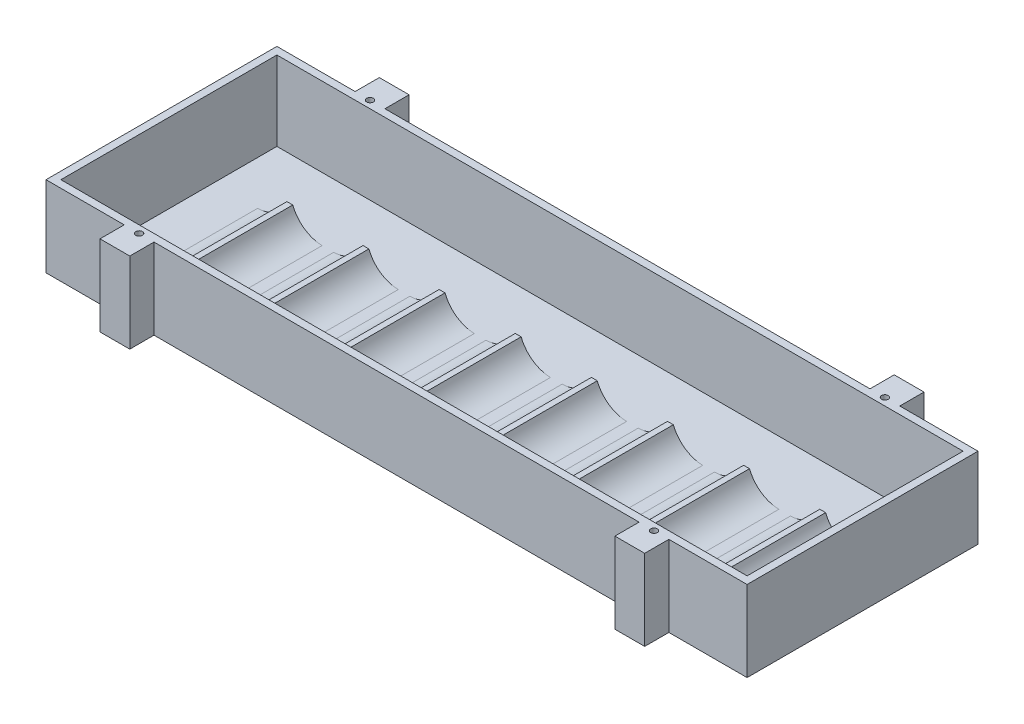
SolidWorks part; units mm, degrees
material "ABS"
ref_plane "Front Plane" through (0, 0, 0) normal (0, 0, 1) x (1, 0, 0)
ref_plane "Top Plane" through (0, 0, 0) normal (0, 1, 0) x (1, 0, 0)
ref_plane "Right Plane" through (0, 0, 0) normal (1, 0, 0) x (0, 0, -1)
sketch "Sketch1" plane through (0, 0, 0) normal (0, 1, 0) x (1, 0, 0)
  line L0 (2.54, -2.54) -> (2.54, -76.2)
  line L1 (0, 0) -> (239.08, 0)
  line L2 (0, 0) -> (0, -78.74)
  line L3 (0, -78.74) -> (239.08, -78.74)
  line L4 (239.08, 0) -> (239.08, -78.74)
  line L5 (2.54, -76.2) -> (236.54, -76.2)
  line L6 (236.54, -2.54) -> (236.54, -76.2)
  line L7 (2.54, -2.54) -> (236.54, -2.54)
  line L8 (0, 0) -> (0, 8.255)
  line L9 (0, 8.255) -> (239.08, 8.255)
  line L10 (239.08, 8.255) -> (239.08, 0)
  line L11 (0, -78.74) -> (0, -86.995)
  line L12 (0, -86.995) -> (239.08, -86.995)
  line L13 (239.08, -86.995) -> (239.08, -78.74)
  dimension "D1" = 73.66
  dimension "D2" = 234
  dimension "D4" = 10.795
  dimension "D5" = 95.25
  dimension "D3" = 2.54
extrude "Boss-Extrude1" add sketch "Sketch1" against normal blind 0.508 contours L2 L3 L4 L1
extrude "Boss-Extrude2" add sketch "Sketch1<3>" along normal blind 27 contours L10 L9 L8 L1 | L12 L13 L3 L11 | L4 L1 L2 L3 L0 L7 L6 L5 region at (119.54, 0, -4.1275) region at (119.54, 0, 2.5171) region at (119.54, 0, 82.8675)
sketch "Sketch1<3>" plane through (0, 0, 0) normal (0, 1, 0) x (1, 0, 0) same geometry as "Sketch1"
sketch "Sketch2" plane through (0, 0, 0) normal (0, 1, 0) x (-1, 0, 0)
  line L0 (-28.54, 0) -> (-28.54, 78.74) construction
  line L1 (-2.54, 2.54) -> (-2.54, 76.2) construction
  line L2 (-17.54, 0) -> (-17.54, 78.74) construction
  line L9 (0, 0) -> (-239.08, 0) construction
  line L10 (0, 78.74) -> (-239.08, 78.74) construction
  dimension "D1" = 26
  dimension "D2" = 15
sketch "Sketch5" plane through (0, 0, 2.54) normal (0, 0, 1) x (1, 0, 0)
  line L0 (28.54, 0) -> (28.54, 7) construction
  line L1 (29.54, 7) -> (27.54, 7)
  line L2 (0, 0) -> (239.08, 0) construction
  line L3 (17.54, 0) -> (39.54, 0)
  line L16 (55.4988, 7) -> (53.4988, 7)
  line L17 (43.4988, 0) -> (65.4988, 0)
  line L18 (54.4988, 0) -> (54.4988, 7) construction
  line L19 (81.4576, 7) -> (79.4576, 7)
  line L20 (69.4576, 0) -> (91.4576, 0)
  line L21 (80.4576, 0) -> (80.4576, 7) construction
  line L22 (107.4164, 7) -> (105.4164, 7)
  line L23 (95.4164, 0) -> (117.4164, 0)
  line L24 (106.4164, 0) -> (106.4164, 7) construction
  line L25 (133.3752, 7) -> (131.3752, 7)
  line L26 (121.3752, 0) -> (143.3752, 0)
  line L27 (132.3752, 0) -> (132.3752, 7) construction
  line L28 (159.334, 7) -> (157.334, 7)
  line L29 (147.334, 0) -> (169.334, 0)
  line L30 (158.334, 0) -> (158.334, 7) construction
  line L37 (170.06, 7) -> (168.06, 7) [skipped]
  line L38 (158.06, 0) -> (180.06, 0) [skipped]
  line L39 (169.06, 0) -> (169.06, 7) construction
  line L40 (145.64, 0) -> (145.64, 7) construction
  line L41 (134.64, 0) -> (156.64, 0) [skipped]
  line L42 (146.64, 7) -> (144.64, 7) [skipped]
  line L43 (122.22, 0) -> (122.22, 7) construction
  line L44 (111.22, 0) -> (133.22, 0) [skipped]
  line L45 (123.22, 7) -> (121.22, 7) [skipped]
  line L46 (98.8, 0) -> (98.8, 7) construction
  line L47 (87.8, 0) -> (109.8, 0) [skipped]
  line L48 (99.8, 7) -> (97.8, 7) [skipped]
  line L49 (75.38, 0) -> (75.38, 7) construction
  line L50 (64.38, 0) -> (86.38, 0) [skipped]
  line L51 (76.38, 7) -> (74.38, 7) [skipped]
  line L52 (51.96, 0) -> (51.96, 7) construction
  line L53 (40.96, 0) -> (62.96, 0) [skipped]
  line L54 (52.96, 7) -> (50.96, 7) [skipped]
  line L55 (185.2928, 7) -> (183.2928, 7)
  line L56 (173.2928, 0) -> (195.2928, 0)
  line L57 (184.2928, 0) -> (184.2928, 7) construction
  line L58 (211.2516, 7) -> (209.2516, 7)
  line L59 (199.2516, 0) -> (221.2516, 0)
  line L60 (210.2516, 0) -> (210.2516, 7) construction
  arc A0 (17.54, 0) -> (27.54, 7) centre (17.292, 10.9972) ccw
  arc A1 (39.54, 0) -> (29.54, 7) centre (39.788, 10.9972) cw
  arc A10 (65.4988, 0) -> (55.4988, 7) centre (65.7468, 10.9972) cw
  arc A11 (43.4988, 0) -> (53.4988, 7) centre (43.2508, 10.9972) ccw
  arc A12 (91.4576, 0) -> (81.4576, 7) centre (91.7056, 10.9972) cw
  arc A13 (69.4576, 0) -> (79.4576, 7) centre (69.2096, 10.9972) ccw
  arc A14 (117.4164, 0) -> (107.4164, 7) centre (117.6644, 10.9972) cw
  arc A15 (95.4164, 0) -> (105.4164, 7) centre (95.1684, 10.9972) ccw
  arc A16 (143.3752, 0) -> (133.3752, 7) centre (143.6232, 10.9972) cw
  arc A17 (121.3752, 0) -> (131.3752, 7) centre (121.1272, 10.9972) ccw
  arc A18 (169.334, 0) -> (159.334, 7) centre (169.582, 10.9972) cw
  arc A19 (147.334, 0) -> (157.334, 7) centre (147.086, 10.9972) ccw
  arc A24 (180.06, 0) -> (170.06, 7) centre (180.308, 10.9972) cw [skipped]
  arc A25 (158.06, 0) -> (168.06, 7) centre (157.812, 10.9972) ccw [skipped]
  arc A26 (134.64, 0) -> (144.64, 7) centre (134.392, 10.9972) ccw [skipped]
  arc A27 (156.64, 0) -> (146.64, 7) centre (156.888, 10.9972) cw [skipped]
  arc A28 (111.22, 0) -> (121.22, 7) centre (110.972, 10.9972) ccw [skipped]
  arc A29 (133.22, 0) -> (123.22, 7) centre (133.468, 10.9972) cw [skipped]
  arc A30 (87.8, 0) -> (97.8, 7) centre (87.552, 10.9972) ccw [skipped]
  arc A31 (109.8, 0) -> (99.8, 7) centre (110.048, 10.9972) cw [skipped]
  arc A32 (64.38, 0) -> (74.38, 7) centre (64.132, 10.9972) ccw [skipped]
  arc A33 (86.38, 0) -> (76.38, 7) centre (86.628, 10.9972) cw [skipped]
  arc A34 (62.96, 0) -> (52.96, 7) centre (63.208, 10.9972) cw [skipped]
  arc A35 (40.96, 0) -> (50.96, 7) centre (40.712, 10.9972) ccw [skipped]
  arc A36 (195.2928, 0) -> (185.2928, 7) centre (195.5408, 10.9972) cw
  arc A37 (173.2928, 0) -> (183.2928, 7) centre (173.0448, 10.9972) ccw
  arc A38 (221.2516, 0) -> (211.2516, 7) centre (221.4996, 10.9972) cw
  arc A39 (199.2516, 0) -> (209.2516, 7) centre (199.0036, 10.9972) ccw
  dimension "D2" = 11
  dimension "D1" = 1
  dimension "D3" = 7
  dimension "D4" = 6
  dimension "D5" = 8
extrude "Boss-Extrude3" add sketch "Sketch5" along normal blind 32.5 from offset 21.59
extrude "Boss-Extrude4" add sketch "Sketch1<4>" against normal up to surface (0.508 mm away) contours L10 L9 L8 L1 | L12 L13 L3 L11 region at (119.54, 0, -4.1275) region at (119.54, 0, 82.8675) up to face at (119.54, -0.508, 39.37)
sketch "Sketch1<4>" plane through (0, 0, 0) normal (0, 1, 0) x (1, 0, 0) same geometry as "Sketch1"
sketch "Sketch6" plane through (0, 27, 0) normal (0, 1, 0) x (1, 0, 0)
  line L0 (0, 0) -> (239.08, 0) construction
  line L1 (239.08, 8.255) -> (239.08, -86.995) construction
  line L2 (0, -86.995) -> (0, 8.255) construction
  line L3 (0, -39.37) -> (14.6137, -39.37) construction
  point P5 (31.75, 0)
  point P6 (207.33, 0)
  point P9 (207.33, -78.74)
  point P10 (31.75, -78.74)
  dimension "D1" = 31.75
  dimension "D2" = 31.75
hole_wizard "#4-40 Tapped Hole2" positions "Sketch10" profile "Sketch9" tap size "#4-40" standard "Ansi Inch"
sketch "Sketch10" plane through (0, 27, 0) normal (0, 1, 0) x (-1, 0, 0)
  point P0 (-31.75, 0)
  point P1 (-207.33, 0)
  point P8 (-31.75, 78.74)
  point P11 (-207.33, 78.74)
sketch "Sketch9" plane through (31.75, 27, 0) normal (1, 0, 0) x (0, 0, 1)
  line L0 (0, 0) -> (0, 8.2992)
  line L1 (0, 8.2992) -> (1.1303, 7.62)
  line L2 (1.1303, 7.62) -> (1.1303, 0)
  line L5 (1.1303, 0) -> (0, 0)
  line L10 (0, 8.2992) -> (-1.1303, 7.62) construction
  line L11 (0, -6.35) -> (0, 107.95) construction
  dimension "Tap Drill Dia." = 2.2606
  dimension "Tap Drill Depth" = 7.62
  dimension "Drill Angle" = 118
cosmetic thread "Hole Thread2" parameters "D1"=5.588, "D2"=2.8448
cosmetic thread "Hole Thread3" parameters "D1"=5.588, "D2"=2.8448
cosmetic thread "Hole Thread4" parameters "D1"=5.588, "D2"=2.8448
cosmetic thread "Hole Thread5" parameters "D1"=5.588, "D2"=2.8448
sketch "Sketch12" plane through (0, 27, 0) normal (0, 1, 0) x (1, 0, 0)
  line L0 (119.54, 8.255) -> (119.54, -86.995) construction
  line L1 (0, 8.255) -> (239.08, 8.255) construction
  line L2 (0, -86.995) -> (239.08, -86.995) construction
sketch "Sketch13" plane through (0, 27, 0) normal (0, 1, 0) x (1, 0, 0)
  line L0 (0, 8.255) -> (239.08, 8.255) construction
  line L1 (36.83, 8.255) -> (202.25, 8.255)
  line L2 (36.83, 8.255) -> (36.83, 0)
  line L3 (36.83, 0) -> (202.25, 0)
  line L4 (202.25, 8.255) -> (202.25, 0)
  line L5 (2.54, -2.54) -> (236.54, -2.54) construction
  line L6 (0, -39.37) -> (14.211, -39.37) construction
  line L7 (0, -86.995) -> (0, 8.255) construction
  line L8 (202.25, -86.995) -> (202.25, -78.74)
  line L9 (36.83, -78.74) -> (202.25, -78.74)
  line L10 (36.83, -86.995) -> (202.25, -86.995)
  line L11 (36.83, -86.995) -> (36.83, -78.74)
  line L12 (2.54, -2.54) -> (236.54, -2.54) construction
  line L13 (0, 8.255) -> (26.67, 8.255)
  line L14 (0, 8.255) -> (0, 0)
  line L15 (0, 0) -> (26.67, 0)
  line L16 (26.67, 8.255) -> (26.67, 0)
  line L17 (119.54, 8.255) -> (119.54, -13.155) construction
  line L18 (212.41, 8.255) -> (212.41, 0)
  line L19 (239.08, 0) -> (212.41, 0)
  line L20 (239.08, 8.255) -> (239.08, 0)
  line L21 (239.08, 8.255) -> (212.41, 8.255)
  line L22 (212.41, -86.995) -> (212.41, -78.74)
  line L23 (239.08, -78.74) -> (212.41, -78.74)
  line L24 (239.08, -86.995) -> (212.41, -86.995)
  line L25 (239.08, -86.995) -> (239.08, -78.74)
  line L26 (26.67, -86.995) -> (26.67, -78.74)
  line L27 (0, -78.74) -> (26.67, -78.74)
  line L28 (0, -86.995) -> (0, -78.74)
  line L29 (0, -86.995) -> (26.67, -86.995)
  dimension "D1" = 5.08
  dimension "D2" = 5.08
  dimension "D3" = 2.54
  dimension "D4" = 2.54
  dimension "D5" = 5.08
extrude "Cut-Extrude1" cut sketch "Sketch13" against normal through all
